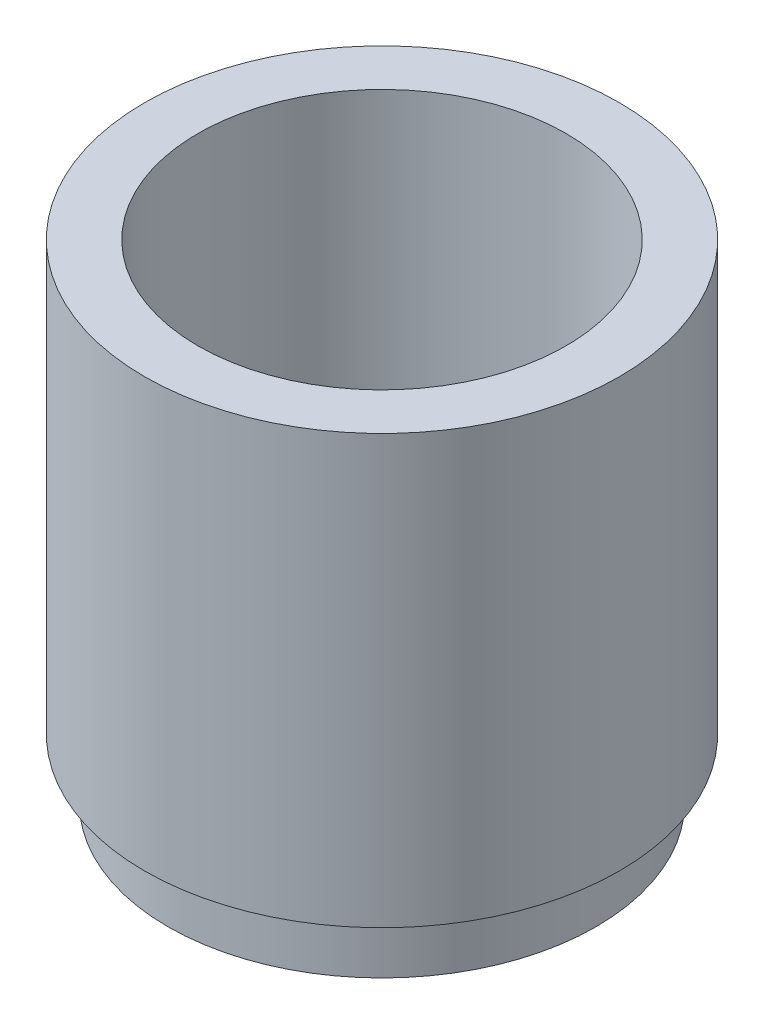
SolidWorks part; units mm, degrees
ref_plane "Front Plane" through (0, 0, 0) normal (0, 0, 1) x (1, 0, 0)
ref_plane "Top Plane" through (0, 0, 0) normal (0, 1, 0) x (1, 0, 0)
ref_plane "Right Plane" through (0, 0, 0) normal (1, 0, 0) x (0, 0, -1)
sketch "Sketch1" plane through (0, 0, 0) normal (0, 1, 0) x (1, 0, 0)
  circle A0 centre (0, 0) radius 8.025
  circle A1 centre (0, 0) radius 6.4
  dimension "D1" = 16.05
  dimension "D2" = 12.8
extrude "Boss-Extrude1" add sketch "Sketch1" along normal blind 2.25
sketch "Sketch2" plane through (0, 2.25, 0) normal (0, 1, 0) x (1, 0, 0)
  circle A0 centre (0, 0) radius 8.9
  circle A1 centre (0, 0) radius 6.9
  dimension "D1" = 17.8
  dimension "D2" = 13.8
extrude "Boss-Extrude2" add sketch "Sketch2" along normal blind 16.05
